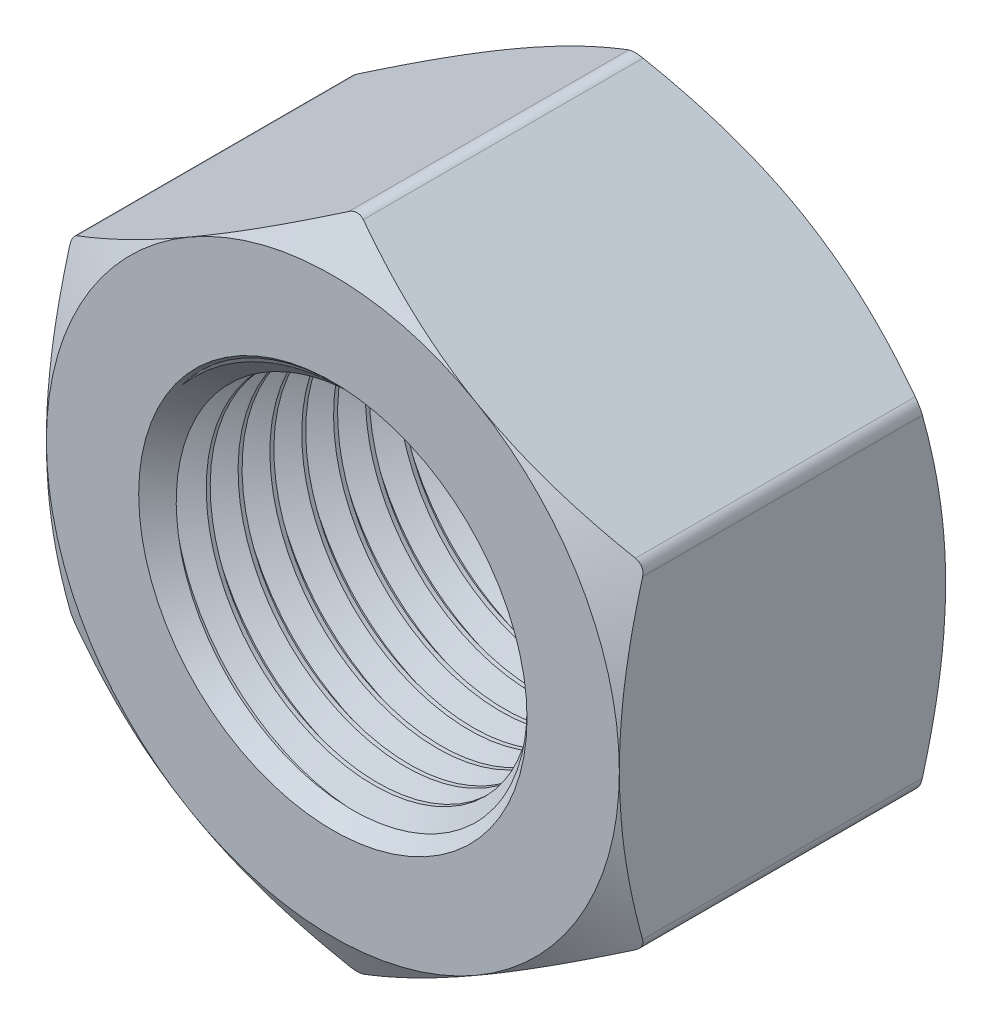
SolidWorks part; units mm, degrees
ref_plane "Front" through (0, 0, 0) normal (0, 0, 1) x (1, 0, 0)
ref_plane "Top" through (0, 0, 0) normal (0, 1, 0) x (1, 0, 0)
ref_plane "Right" through (0, 0, 0) normal (1, 0, 0) x (0, 0, -1)
sketch "Sketch1" plane through (0, 0, 0) normal (0, 0, 1) x (1, 0, 0)
  line L0 (0, 9.525) -> (0, 7.9375) construction
  line L1 (-14.2875, 8.2489) -> (-14.2875, -8.2489)
  line L2 (-14.2875, -8.2489) -> (0, -16.4978)
  line L3 (0, -16.4978) -> (14.2875, -8.2489)
  line L4 (14.2875, -8.2489) -> (14.2875, 8.2489)
  line L5 (14.2875, 8.2489) -> (0, 16.4978)
  line L6 (0, 16.4978) -> (-14.2875, 8.2489)
  circle A0 centre (0, 0) radius 14.2875 construction
  circle A1 centre (0, 0) radius 9.525 construction
  point P10 (0, 9.525)
  dimension "Width" = 28.575
  dimension "Thread Size" = 19.05
  dimension "Thread Pitch" = 1.5875
sketch "Sketch2" plane through (0, 0, 0) normal (1, 0, 0) x (0, 0, -1)
  line L0 (-8.1359, 0) -> (8.1359, 0) construction
  line L1 (-8.1359, 16.4978) -> (8.1359, 16.4978) construction
  dimension "Height" = 16.2719
sketch "Sketch15" plane through (0, 0, 0) normal (0, 0, 1) x (1, 0, 0)
  line L1 (0, 16.4978) -> (-14.2875, 8.2489)
  line L2 (-14.2875, 8.2489) -> (-14.2875, -8.2489)
  line L3 (-14.2875, -8.2489) -> (0, -16.4978)
  line L4 (0, -16.4978) -> (14.2875, -8.2489)
  line L5 (14.2875, -8.2489) -> (14.2875, 8.2489)
  line L6 (14.2875, 8.2489) -> (0, 16.4978)
  circle A0 centre (0, 0) radius 14.2875 construction
extrude "Boss-Extrude2" add sketch "Sketch15" along normal mid plane 16.2719
sketch "Sketch16" plane through (0, 0, 0) normal (0, 0, 1) x (1, 0, 0)
  circle A0 centre (0, 0) radius 9.525 construction
  circle A1 centre (0, 0) radius 9.525
sketch "Sketch4" plane through (0, 0, -8.1359) normal (0, 0, -1) x (-1, 0, 0)
  circle A0 centre (0, 0) radius 9.525 construction
  circle A1 centre (0, 0) radius 9.525
extrude "Cut-Extrude4" cut sketch "Sketch16" against normal through all both and the other way through all
sketch "Sketch7" plane through (0, 0, 8.1359) normal (0, 0, 1) x (1, 0, 0)
  circle A0 centre (0, 0) radius 14.2875 construction
  circle A1 centre (0, 0) radius 14.2875
extrude "Cut-Extrude5" cut sketch "Sketch7" against normal through all draft 60 flip side to cut
mirror "Mirror4" about plane through (0, 0, 0) normal (0, 0, 1) of "Cut-Extrude5"
fillet "Fillet2" radius 0.7144 6 edges at (-14.2875, 8.2489, 0) (-14.2875, -8.2489, 0) (0, -16.4978, 0) (14.2875, -8.2489, 0) (14.2875, 8.2489, 0) (0, 16.4978, 0)
sketch "Sketch8" plane through (0, 0, 8.1359) normal (0, 0, 1) x (1, 0, 0)
  line L0 (2.4653, -9.2004) -> (0, 0) construction
  line L2 (0, 9.525) -> (0, 7.9375) construction
  circle A0 centre (0, 0) radius 9.525 construction
  point P0 (2.4653, -9.2004)
  dimension "D1" = 15
sketch "Sketch13" plane through (0, 0, -8.1359) normal (0, 0, -1) x (-1, 0, 0)
  circle A0 centre (0, 0) radius 9.525 construction
  circle A1 centre (0, 0) radius 9.525
extrude "Boss-Extrude1" add sketch "Sketch13" against normal up to surface (16.2719 mm away) separate body up to face at (9.525, 0, 8.1359)
curve "Helix/Spiral3" pitch 1.5875 height 17.8594 radius 9.525 centre (0, 0, -8.1359) axis (0, 0, 1) start towards (0, 1, 0)
sketch "Sketch12" plane through (0, 0, 0) normal (1, 0, 0) x (0, 0, -1)
  line L0 (9.525, 9.525) -> (8.1359, 9.525)
  line L1 (9.525, 9.525) -> (8.9297, 8.4939)
  line L2 (8.9297, 8.4939) -> (8.7312, 8.4939)
  line L3 (8.7312, 8.4939) -> (8.1359, 9.525)
  line L4 (8.8305, 8.4939) -> (8.8305, 9.525) construction
  line L5 (8.4336, 9.0094) -> (9.2273, 9.0094) construction
  dimension "D1" = 60
  dimension "D2" = 0.1984
  dimension "D3" = 0.7937
sweep "Cut-Sweep1" cut profiles "Sketch12" path "Helix/Spiral3" align with end faces yes
sketch "Sketch17" plane through (0, 0, 8.1359) normal (0, 0, 1) x (1, 0, 0)
  circle A1 centre (0, 0) radius 9.525
  circle A2 centre (0, 0) radius 9.525
  dimension "D1" = 0
extrude "Boss-Extrude3" add sketch "Sketch17" against normal up to surface (16.2719 mm away) up to face at (9.525, 0, -8.1359)
combine bodies "Combine1" operation type subtract main body 127 bodies to subtract 118
sketch "Sketch10" plane through (0, 0, 8.1359) normal (0, 0, 1) x (1, 0, 0)
  circle A0 centre (0, 0) radius 9.525 construction
  circle A1 centre (0, 0) radius 9.525 construction
  circle A2 centre (0, 0) radius 9.6837
  dimension "D1" = 0.1588
extrude "Cut-Extrude2" cut sketch "Sketch10" against normal through all draft 45
sketch "Sketch11" plane through (0, 0, -8.1359) normal (0, 0, -1) x (-1, 0, 0)
  circle A1 centre (0, 0) radius 9.6837 construction
  circle A2 centre (0, 0) radius 9.6837
extrude "Cut-Extrude3" cut sketch "Sketch11" against normal through all draft 45
equation "\"D1\"= \"Height@Sketch2\""
equation "\"D3@Helix/Spiral3\"=\"Height@Sketch2\"+\"Thread Pitch@Sketch1\""
equation "\"D4@Helix/Spiral3\"=\"Thread Pitch@Sketch1\""
equation "\"D2@Sketch12\" = \"D4@Helix/Spiral3\"*.125"
equation "\"D3@Sketch12\" = \"D4@Helix/Spiral3\"*.50"
equation "\"D1@Boss-Extrude2\"=\"Height@Sketch2\""
equation "\"D1@Fillet2\"=\"Width@Sketch1\"*0.025"
equation "\"D1@Sketch10\"=\"Thread Pitch@Sketch1\"*0.1"
